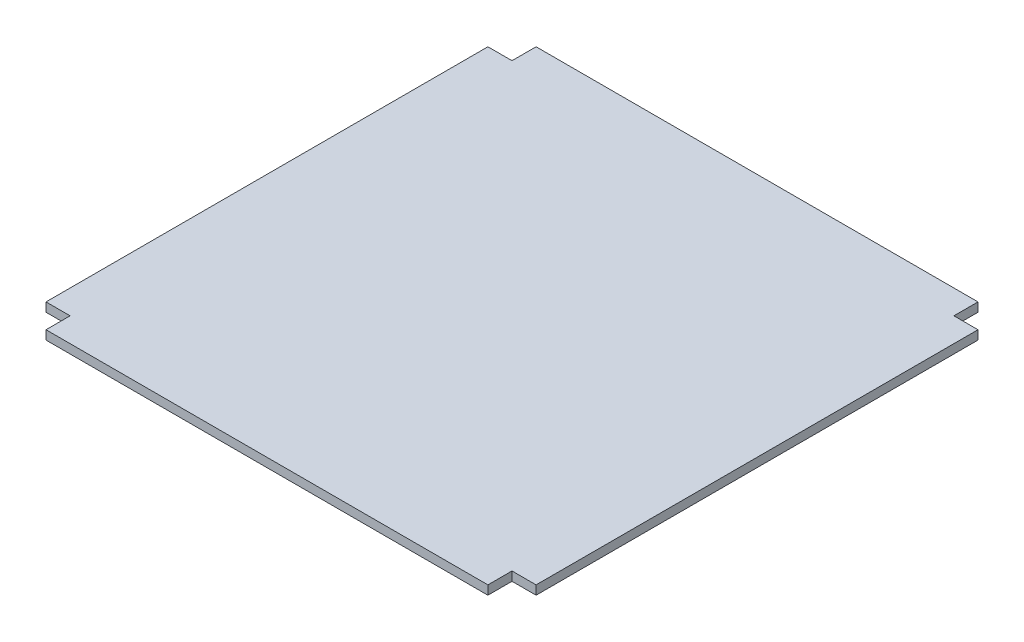
SolidWorks part; units mm, degrees
material "Acrylic (Medium-high impact)"
ref_plane "Front Plane" through (0, 0, 0) normal (0, 0, 1) x (1, 0, 0)
ref_plane "Top Plane" through (0, 0, 0) normal (0, 1, 0) x (1, 0, 0)
ref_plane "Right Plane" through (0, 0, 0) normal (1, 0, 0) x (0, 0, -1)
sketch "Sketch2" plane through (0, 0, 0) normal (0, 1, 0) x (1, 0, 0)
  line L0 (0, 289.814) -> (0, 14.986)
  line L1 (0, 0) -> (304.8, 0) construction
  line L2 (0, 0) -> (0, 304.8) construction
  line L3 (0, 304.8) -> (304.8, 304.8) construction
  line L4 (304.8, 0) -> (304.8, 304.8) construction
  line L5 (0, 304.8) -> (14.986, 304.8) construction
  line L6 (0, 304.8) -> (0, 289.814) construction
  line L7 (0, 289.814) -> (14.986, 289.814)
  line L8 (14.986, 304.8) -> (14.986, 289.814)
  line L9 (0, 0) -> (14.986, 0) construction
  line L10 (0, 0) -> (0, 14.986) construction
  line L11 (0, 14.986) -> (14.986, 14.986)
  line L12 (14.986, 0) -> (14.986, 14.986)
  line L13 (304.8, 0) -> (289.814, 0) construction
  line L14 (304.8, 0) -> (304.8, 14.986) construction
  line L15 (304.8, 14.986) -> (289.814, 14.986)
  line L16 (289.814, 0) -> (289.814, 14.986)
  line L17 (304.8, 304.8) -> (289.814, 304.8) construction
  line L18 (304.8, 304.8) -> (304.8, 289.814) construction
  line L19 (304.8, 289.814) -> (289.814, 289.814)
  line L20 (289.814, 304.8) -> (289.814, 289.814)
  line L21 (14.986, 304.8) -> (289.814, 304.8)
  line L22 (304.8, 289.814) -> (304.8, 14.986)
  line L23 (289.814, 0) -> (14.986, 0)
  dimension "D1" = 304.8
  dimension "D2" = 304.8
  dimension "D3" = 14.986
extrude "Boss-Extrude1" add sketch "Sketch2" along normal blind 5.588
